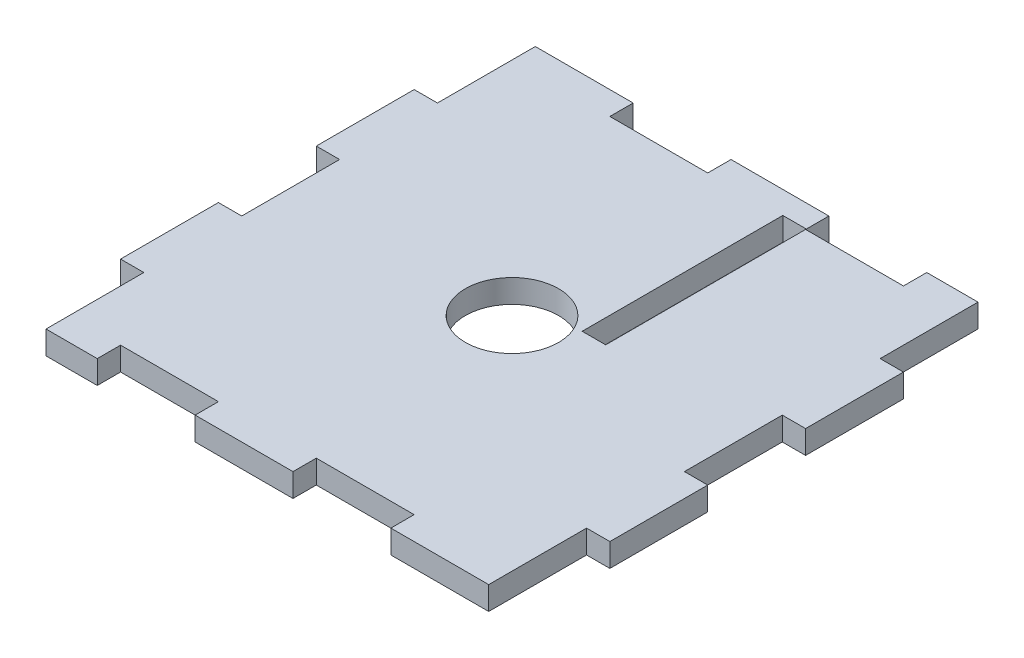
SolidWorks part; units mm, degrees
ref_plane "Front Plane" through (0, 0, 0) normal (0, 0, 1) x (1, 0, 0)
ref_plane "Top Plane" through (0, 0, 0) normal (0, 1, 0) x (1, 0, 0)
ref_plane "Right Plane" through (0, 0, 0) normal (1, 0, 0) x (0, 0, -1)
sketch "Sketch2" plane through (0, 100, 0) normal (0, 1, 0) x (1, 0, 0)
  line L36 (40, 100) -> (40, 95.2375)
  line L37 (40, 95.2375) -> (20, 95.2375)
  line L38 (20, 95.2375) -> (20, 100)
  line L39 (20, 100) -> (0, 100)
  line L40 (0, 100) -> (0, 80)
  line L41 (0, 80) -> (-4.7625, 80)
  line L42 (-4.7625, 80) -> (-4.7625, 60)
  line L43 (-4.7625, 60) -> (0, 60)
  line L44 (0, 60) -> (0, 40)
  line L45 (0, 40) -> (-4.7625, 40)
  line L46 (-4.7625, 40) -> (-4.7625, 20)
  line L47 (-4.7625, 20) -> (0, 20)
  line L48 (0, 20) -> (0, 0)
  line L49 (0, 0) -> (10.475, 0)
  line L50 (10.475, 0) -> (10.475, 4.7625)
  line L51 (10.475, 4.7625) -> (30.475, 4.7625)
  line L52 (30.475, 4.7625) -> (30.475, 0)
  line L53 (30.475, 0) -> (50.475, 0)
  line L54 (50.475, 0) -> (50.475, 4.7625)
  line L55 (50.475, 4.7625) -> (70.475, 4.7625)
  line L56 (70.475, 4.7625) -> (70.475, 0)
  line L57 (70.475, 0) -> (90.475, 0)
  line L58 (90.475, 0) -> (90.475, 20)
  line L59 (90.475, 20) -> (95.2375, 20)
  line L60 (95.2375, 20) -> (95.2375, 40)
  line L61 (95.2375, 40) -> (90.475, 40)
  line L62 (90.475, 40) -> (90.475, 60)
  line L63 (90.475, 60) -> (95.2375, 60)
  line L64 (95.2375, 60) -> (95.2375, 80)
  line L65 (95.2375, 80) -> (90.475, 80)
  line L66 (90.475, 80) -> (90.475, 100)
  line L67 (90.475, 100) -> (80, 100)
  line L68 (80, 100) -> (80, 95.2375)
  line L69 (80, 95.2375) -> (60, 95.2375)
  line L70 (60, 95.3929) -> (60, 100)
  line L71 (60, 100) -> (40, 100)
  line L72 (40, 100) -> (40, 95.2375)
  line L73 (40, 95.2375) -> (20, 95.2375)
  line L74 (20, 95.2375) -> (20, 100)
  line L75 (20, 100) -> (0, 100)
  line L76 (0, 100) -> (0, 80)
  line L77 (0, 80) -> (-4.7625, 80)
  line L78 (-4.7625, 80) -> (-4.7625, 60)
  line L79 (-4.7625, 60) -> (0, 60)
  line L80 (0, 60) -> (0, 40)
  line L81 (0, 40) -> (-4.7625, 40)
  line L82 (-4.7625, 40) -> (-4.7625, 20)
  line L83 (-4.7625, 20) -> (0, 20)
  line L84 (0, 20) -> (0, 0)
  line L85 (0, 0) -> (10.475, 0)
  line L86 (10.475, 0) -> (10.475, 4.7625)
  line L87 (10.475, 4.7625) -> (30.475, 4.7625)
  line L88 (30.475, 4.7625) -> (30.475, 0)
  line L89 (30.475, 0) -> (50.475, 0)
  line L90 (50.475, 0) -> (50.475, 4.7625)
  line L91 (50.475, 4.7625) -> (70.475, 4.7625)
  line L92 (70.475, 4.7625) -> (70.475, 0)
  line L93 (70.475, 0) -> (90.475, 0)
  line L94 (90.475, 0) -> (90.475, 20)
  line L95 (90.475, 20) -> (95.2375, 20)
  line L96 (95.2375, 20) -> (95.2375, 40)
  line L97 (95.2375, 40) -> (90.475, 40)
  line L98 (90.475, 40) -> (90.475, 60)
  line L99 (90.475, 60) -> (95.2375, 60)
  line L100 (95.2375, 60) -> (95.2375, 80)
  line L101 (95.2375, 80) -> (90.475, 80)
  line L102 (90.475, 80) -> (90.475, 100)
  line L103 (90.475, 100) -> (80, 100)
  line L104 (80, 100) -> (80, 95.2375)
  line L105 (80, 95.2375) -> (60, 95.2375)
  line L107 (60, 100) -> (40, 100)
  line L185 (55.1899, 54.3869) -> (55.1899, 95.3929)
  line L186 (55.1899, 54.3869) -> (55.1899, 95.3929)
  line L187 (60, 95.2375) -> (60, 54.3869)
  line L188 (60, 95.2375) -> (60, 54.3869)
  line L269 (60, 95.3929) -> (60, 100)
  line L270 (55.1899, 95.3929) -> (60, 95.3929)
  line L271 (55.1899, 95.3929) -> (60, 95.3929)
  line L272 (60, 54.3869) -> (55.1899, 54.3869)
  line L273 (60, 54.3869) -> (55.1899, 54.3869)
  dimension "D1" = 0
extrude "Boss-Extrude1" add sketch "Sketch2" against normal blind 4.7625
sketch "Sketch3" plane through (0, 100, 0) normal (0, 1, 0) x (1, 0, 0)
  circle A0 centre (45.2375, 50) radius 9.525 construction
  circle A1 centre (45.2375, 50) radius 9.525
extrude "Cut-Extrude1" cut sketch "Sketch3" against normal blind 4.7625
